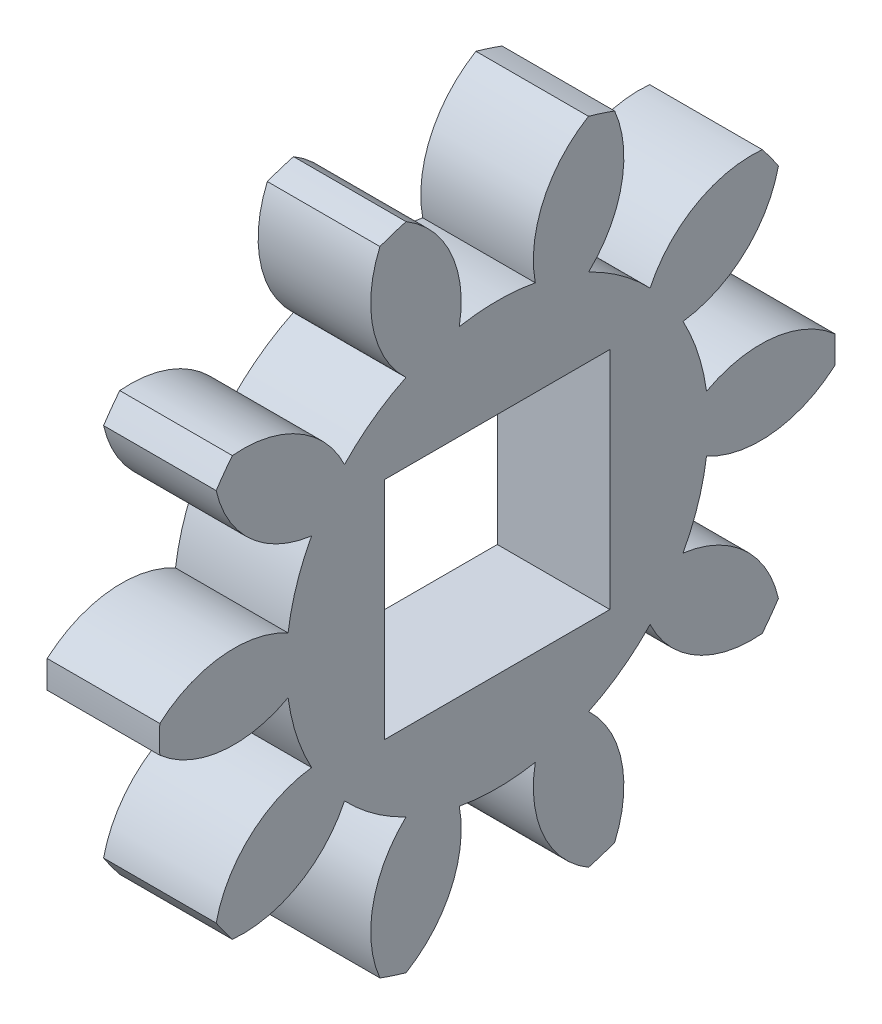
SolidWorks part; units mm, degrees
ref_plane "Plane1" through (0, 0, 0) normal (0, 0, 1) x (1, 0, 0)
ref_plane "Plane2" through (0, 0, 0) normal (0, 1, 0) x (1, 0, 0)
ref_plane "Plane3" through (0, 0, 0) normal (1, 0, 0) x (0, 0, -1)
other "Configuration Table"
sketch "HoldingSke" plane through (0, 0, 0) normal (0, 1, 0) x (1, 0, 0)
  line L0 (0, 0) -> (0.4924, -0.0868)
  line L1 (-15, 0) -> (100, 0) construction
  line L2 (0, 0) -> (-2.1039, 2.3779)
  line L3 (0, 0) -> (-11.863, 4.5341)
  line L4 (0, 0) -> (8.5048, 1.4996)
  line L5 (0, 0) -> (-46.8476, -17.4728)
  line L6 (0, 0) -> (-3.3159, -2.2372)
  line L7 (-2.1039, 2.3779) -> (8.6586, 51.2059)
  line L8 (-76.2, 54.61) -> (-75.9, 54.61)
  line L9 (-67.7845, 28.3722) -> (-49.3413, 33.142)
  line L10 (-76.2, 71.12) -> (104.1128, 71.12)
  line L11 (0, 0) -> (-4, 0)
  line L12 (-76.2, 101.6) -> (-76.133, 101.6)
  line L13 (24.9733, 27.94) -> (52.9518, 28.4284)
  line L14 (24.9733, 27.94) -> (24.9743, 27.94)
  line L15 (24.9733, 27.94) -> (100.4006, 29.5858)
  line L16 (-63.627, -2) -> (-12.827, -2)
  circle A0 centre (0, 0) radius 1
  circle A1 centre (0, 0) radius 7.499
  circle A2 centre (0, 0) radius 37.5
  circle A3 centre (0, 0) radius 1
  dimension "MHD" = 14.998
  dimension "Hub_dia" = 75
  dimension "Bore" = 2
  dimension "MBD" = 2
  dimension "Num_teeth" = 10
  dimension "Pitch" = 0.5
  dimension "Overall_len" = 50
  dimension "Show_teeth" = 10
  dimension "Thickness" = 4
  dimension "OAL" = 50.0001
  dimension "T_dim" = 0.3
  dimension "Ap" = 14.5
  dimension "H" = 19.05
  dimension "Pitch_radius" = 180.3128
  dimension "Width" = 4
  dimension "Backlash" = 0.067
  dimension "Addendum_fac" = 1
  dimension "Dedendum_fac" = 1.25
  dimension "Clearance_fac" = 0.25
  dimension "Dedendum_add" = 0.001
  dimension "Module" = 2
sketch "BasProSke" plane through (0, 0, 0) normal (0, 1, 0) x (1, 0, 0)
  line L0 (-10, 0) -> (60, 0) construction
  line L1 (0, 0) -> (0, 12)
  line L2 (0, 0) -> (4, 0)
  line L3 (4, 0) -> (4, 12)
  line L4 (4, 12) -> (0, 12)
  dimension "Thickness" = 4
  dimension "Diameter" = 24
revolve "Base-Revolve" add sketch "BasProSke" angle 360 about L0
sketch "TooCutSke" plane through (0, 0, 0) normal (1, 0, 0) x (0, 0, -1)
  line L1 (0, 0) -> (0, 107) construction
  line L2 (0, 0) -> (-1.6814, 9.8576) construction
  line L3 (0, 0) -> (-6.1153, 18.8209) construction
  line L4 (-1.6814, 9.8576) -> (-3.0576, 9.4105) construction
  arc A0 (1.35, 7.3765) -> (-1.35, 7.3765) centre (0, 0) ccw
  arc A1 (3.2708, 11.572) -> (-3.2708, 11.572) centre (0, 0) ccw
  circle A2 centre (0, 0) radius 10 construction
  circle A3 centre (0, 0) radius 9.6815 construction
  arc A4 (-1.35, 7.3765) -> (-3.2708, 11.572) centre (-5.2814, 8.1141) ccw
  arc A5 (3.2708, 11.572) -> (1.35, 7.3765) centre (5.2814, 8.1141) ccw
  dimension "Root_dia" = 14.998
  dimension "Overcut_dia" = 24.0508
  dimension "Pitch_dia" = 20
  dimension "Base_dia" = 19.363
  dimension "Flank_rad" = 4
  dimension "Half_ang" = 18
  dimension "Half_CT" = 1.4471
extrude "ToothCut" cut sketch "TooCutSke" along normal through all
fillet "Breaks" [suppressed] radius 0.04 tangent propagation no
fillet "RootFillets" [suppressed] radius 0.501
pattern_circular "TeethCuts" count 10 every 36 about axis through (-10, 0, 0) along (1, 0, 0) of "ToothCut", "RootFillets", "Breaks"
sketch "HubNeaOneSke" plane through (0, 0, 0) normal (-1, 0, 0) x (0, 0, 1)
  circle A0 centre (0, 0) radius 7.499
  dimension "Diameter" = 14.998
extrude "HubNearOne" [suppressed] add sketch "HubNeaOneSke" along normal blind 46.0001
sketch "HubNeaBotSke" plane through (0, 0, 0) normal (-1, 0, 0) x (0, 0, 1)
  circle A0 centre (0, 0) radius 7.499
  dimension "Diameter" = 14.998
extrude "HubNearBoth" [suppressed] add sketch "HubNeaBotSke" along normal blind 23
ref_plane "FarPln" through (4, 0, 0) normal (1, 0, 0) x (0, 0, -1)
sketch "HubFarSke" plane through (4, 0, 0) normal (1, 0, 0) x (0, 0, -1)
  circle A0 centre (0, 0) radius 7.499
  dimension "Diameter" = 14.998
extrude "HubFar" [suppressed] add sketch "HubFarSke" along normal blind 23
sketch "BorSke" plane through (0, 0, 0) normal (1, 0, 0) x (0, 0, -1)
  circle A0 centre (0, 0) radius 1
  dimension "Diameter" = 2
extrude "Bore" cut sketch "BorSke" along normal mid plane 100.0001
sketch "KeySke" plane through (0, 0, 0) normal (1, 0, 0) x (0, 0, -1)
  line L0 (-0.4, 0) -> (-0.4, 1.3)
  line L1 (-0.4, 1.3) -> (0.4, 1.3)
  line L2 (0.4, 1.3) -> (0.4, 0)
  line L3 (0, 0) -> (0, 34) construction
  line L4 (-0.4, 0) -> (0.4, 0)
  dimension "Offset" = 1.3
  dimension "Width" = 0.8
extrude "Keyway" [suppressed] cut sketch "KeySke" along normal mid plane 100.0001
pattern_circular "Keyway2" [suppressed] count 2 every 90 about axis through (-10, 0, 0) along (1, 0, 0)
sketch "草图1" plane through (0, 0, 0) normal (-1, 0, 0) x (0, 0, 1)
  line L1 (-4, 4) -> (4, 4)
  line L2 (-4, 4) -> (-4, -4)
  line L3 (-4, -4) -> (4, -4)
  line L4 (4, 4) -> (4, -4)
  line L5 (-4, 4) -> (4, -4) construction
  line L6 (-4, -4) -> (4, 4) construction
  point P0 (0, 0)
  dimension "D1" = 8
  dimension "D2" = 8
extrude "切除-拉伸2" cut sketch "草图1" against normal through all
ref_axis "Axis1" through (-80.9, 0, 0) along (1, 0, 0)
equation "' \"Module@HoldingSke\" = 6.35"
equation "' \"Num_teeth@HoldingSke\" = 12"
equation "' \"Ap@HoldingSke\" =  20"
equation "' \"Ap@HoldingSke\" = 20"
equation "' \"Width@HoldingSke\" = 0.5 * 25.4"
equation "' \"Hub_dia@HoldingSke\"= 1 * 25.4"
equation "' \"Hub_dia@HoldingSke\" = 1 * 25.4"
equation "' \"Overall_len@HoldingSke\" = 1.0 * 25.4"
equation "' \"Bore@HoldingSke\" = 0.75 * 25.4"
equation "' \"T_dim@HoldingSke\" = 0.1 * 25.4"
equation "' \"Width@KeySke\" = 0.25 * 25.4"
equation "' \"Show_teeth@HoldingSke\" = 13"
equation "' \"Backlash@HoldingSke\" = 0.009 * 25.4"
equation "' \"Addendum_fac@HoldingSke\" = 1.0"
equation "' \"Dedendum_fac@HoldingSke\" = 1.25"
equation "' \"Dedendum_add@HoldingSke\" = 0.00005 * 25.4"
equation "' \"Clearance_fac@HoldingSke\" = 0.25"
equation "\"Pitch@HoldingSke\" = 1 / \"Module@HoldingSke\""
equation "\"Overcut_dia@TooCutSke\" = (\"Num_teeth@HoldingSke\" + 2 * \"Addendum_fac@HoldingSke\") / \"Pitch@HoldingSke\" + 0.002 * 25.4"
equation "\"Pitch_dia@TooCutSke\" = \"Num_teeth@HoldingSke\" / \"Pitch@HoldingSke\""
equation "\"Base_dia@TooCutSke\" = \"Num_teeth@HoldingSke\" / \"Pitch@HoldingSke\" * cos((\"Ap@HoldingSke\"  * 3.14159265 / 180))"
equation "\"Root_dia@TooCutSke\" = (\"Num_teeth@HoldingSke\" + 2) / \"Pitch@HoldingSke\" - 2 * (\"Addendum_fac@HoldingSke\" + \"Dedendum_fac@HoldingSke\") / \"Pitch@HoldingSke\" - \"Dedendum_add@HoldingSke\" * 2"
equation "\"Half_ang@TooCutSke\" = 180 / \"Num_teeth@HoldingSke\""
equation "\"Half_CT@TooCutSke\" = \"Num_teeth@HoldingSke\" / \"Pitch@HoldingSke\" * sin((3.14159265 / 2 / \"Num_teeth@HoldingSke\")) / 2 - 7 * \"Backlash@HoldingSke\" / 4"
equation "\"Flank_rad@TooCutSke\" = \"Num_teeth@HoldingSke\" / \"Pitch@HoldingSke\" / 5"
equation "\"Radius@RootFillets\" = \"Clearance_fac@HoldingSke\" / \"Pitch@HoldingSke\" + \"Dedendum_add@HoldingSke\""
equation "\"Break_rad@Breaks\" = 0.02 / \"Pitch@HoldingSke\""
equation "\"Thickness@HoldingSke\" = \"Width@HoldingSke\""
equation "\"OAL@HoldingSke\" = \"Thickness@HoldingSke\""
equation "\"MHD@HoldingSke\" = (\"Num_teeth@HoldingSke\" + 2) / \"Pitch@HoldingSke\" - 2 * (\"Addendum_fac@HoldingSke\" + \"Dedendum_fac@HoldingSke\")  / \"Pitch@HoldingSke\" - \"Dedendum_add@HoldingSke\" * 2"
equation "\"MBD@HoldingSke\" = (\"Num_teeth@HoldingSke\" + 2) / \"Pitch@HoldingSke\" - 2 * (\"Addendum_fac@HoldingSke\" + \"Dedendum_fac@HoldingSke\")  / \"Pitch@HoldingSke\" - \"Dedendum_add@HoldingSke\" * 2 - 0.002 * 25.4"
equation "\"MHD@HoldingSke\" = ((sgn( \"MHD@HoldingSke\" - \"Hub_dia@HoldingSke\" )-1)*( \"MHD@HoldingSke\" - \"Hub_dia@HoldingSke\" ))/-2+ \"Hub_dia@HoldingSke\""
equation "\"MBD@HoldingSke\" = ((sgn( \"MBD@HoldingSke\" - \"Bore@HoldingSke\" )-1)*( \"MBD@HoldingSke\" - \"Bore@HoldingSke\" ))/-2+ \"Bore@HoldingSke\""
equation "\"OAL@HoldingSke\" = ((sgn( \"OAL@HoldingSke\" - \"Overall_len@HoldingSke\" )+1)*( \"OAL@HoldingSke\" - \"Overall_len@HoldingSke\" ))/2 + \"Overall_len@HoldingSke\" + 0.000002 * 25.4"
equation "\"Num_teeth@TeethCuts\" = int( \"Show_teeth@HoldingSke\" ) + 1"
equation "\"Num_teeth@TeethCuts\" = ((sgn( \"Num_teeth@TeethCuts\" - \"Num_teeth@HoldingSke\" )-1)*( \"Num_teeth@TeethCuts\" - \"Num_teeth@HoldingSke\" ))/-2+ \"Num_teeth@HoldingSke\""
equation "\"Num_teeth@TeethCuts\" = ((sgn( \"Num_teeth@TeethCuts\" - 2.0)+1)*( \"Num_teeth@TeethCuts\" - 2.0))/2 +2.0"
equation "\"Angle@TeethCuts\" = 360.0 / \"Num_teeth@HoldingSke\""
equation "\"Diameter@BasProSke\" = (\"Num_teeth@HoldingSke\" + 2 * \"Addendum_fac@HoldingSke\") / \"Pitch@HoldingSke\""
equation "\"Thickness@BasProSke\"  = \"Thickness@HoldingSke\""
equation "' \"Fillet_rad@BasProSke\" =  \"Thickness@HoldingSke\" * 0.05"
equation "' \"Fillet_rad@BasProSke\" = \"Thickness@HoldingSke\" * 0.05"
equation "\"MHD@HoldingSke\" = ((sgn( \"MHD@HoldingSke\" - \"Root_dia@TooCutSke\" )-1)*( \"MHD@HoldingSke\" - \"Root_dia@TooCutSke\" ))/-2+ \"Root_dia@TooCutSke\""
equation "\"Diameter@HubNeaOneSke\" = \"MHD@HoldingSke\""
equation "\"Length@HubNearOne\" = \"OAL@HoldingSke\" - \"Thickness@BasProSke\""
equation "\"Diameter@HubNeaBotSke\" = \"MHD@HoldingSke\""
equation "\"Length@HubNearBoth\" = ( \"OAL@HoldingSke\" - \"Thickness@BasProSke\" ) / 2.0"
equation "\"Thickness@FarPln\" = \"Thickness@BasProSke\""
equation "\"Diameter@HubFarSke\" = \"MHD@HoldingSke\""
equation "\"Length@HubFar\" = ( \"OAL@HoldingSke\" - \"Thickness@BasProSke\" ) / 2.0"
equation "\"Diameter@BorSke\" = \"MBD@HoldingSke\""
equation "\"D1@Bore\" = \"OAL@HoldingSke\" * 2.0"
equation "\"D1@Keyway\" = \"OAL@HoldingSke\" * 2.0"
equation "\"Offset@KeySke\" = \"T_dim@HoldingSke\" + \"MBD@HoldingSke\" / 2.0"
